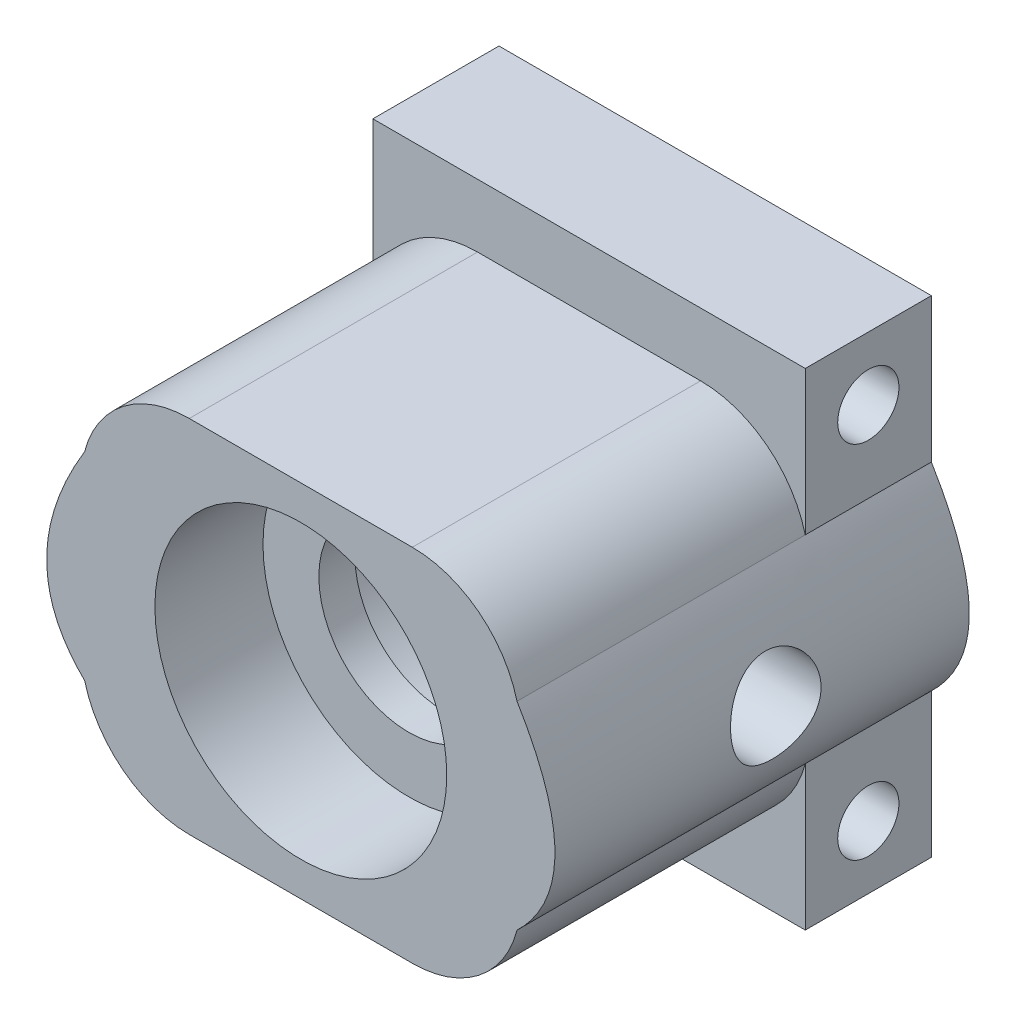
SolidWorks part; units mm, degrees
material "PLA"
ref_plane "Front Plane" through (0, 0, 0) normal (0, 0, 1) x (1, 0, 0)
ref_plane "Top Plane" through (0, 0, 0) normal (0, 1, 0) x (1, 0, 0)
ref_plane "Right Plane" through (0, 0, 0) normal (1, 0, 0) x (0, 0, -1)
sketch "Sketch1" plane through (0, 0, 0) normal (0, 0, 1) x (1, 0, 0)
  line L0 (-12, 13.5) -> (-12, 10)
  line L1 (-12, 10) -> (12, 10)
  line L2 (12, 10) -> (12, 13.5)
  line L3 (12, 13.5) -> (-12, 13.5)
  line L4 (-12, -10) -> (-12, -13.5)
  line L5 (-12, -13.5) -> (12, -13.5)
  line L6 (12, -13.5) -> (12, -10)
  line L7 (12, -10) -> (-12, -10)
  line L8 (0, 10.0333) -> (0, -15.702) construction
  line L9 (-12, 10) -> (-12, -10) construction
  line L10 (12, 10) -> (12, -10) construction
  line L11 (12, 10) -> (12, 5.5)
  line L12 (12, -10) -> (12, -5.5)
  line L13 (10, 10) -> (10, 5.5)
  line L14 (10, -10) -> (10, -5.5)
  line L17 (-10, -10) -> (-10, -5.5)
  line L18 (0, 0) -> (14.9553, 0) construction
  line L19 (-12, -10) -> (-12, -5.5)
  line L20 (-12, 10) -> (-12, 5.5)
  line L21 (-10, 10) -> (-10, 5.5)
  circle A0 centre (0, 0) radius 8.1
  circle A1 centre (0, 0) radius 5
  spline S0 degree 2 poles (12, 5.5) (16.2082, -1.4527) (12, -5.5) knots 0 0 0 0.703674 0.703674 0.703674
  spline S1 degree 2 poles (5.9341, -10) (5.4786, -10.0093) (0, -10) knots 0.968743 0.968743 0.968743 1 1 1
  spline S2 degree 2 poles (10, 5.5) (13.145, -1.5935) (10, -5.5) knots 0 0 0 0.703674 0.703674 0.703674
  spline S3 degree 2 poles (-12, 5.5) (-16.2082, -1.4527) (-12, -5.5) knots 0 0 0 0.703674 0.703674 0.703674
  spline S4 degree 2 poles (-10, 5.5) (-13.145, -1.5935) (-10, -5.5) knots 0 0 0 0.703674 0.703674 0.703674
  point P9 (0, -10)
  point P21 (12, 7.75)
  point P26 (0, 0)
  dimension "D6" = 8
  dimension "D8" = 16.2
  dimension "D9" = 10
  dimension "D5" = 8
  dimension "D1" = 3.5
  dimension "D2" = 3.5
  dimension "D3" = 24
  dimension "D4" = 27
  dimension "D7" = 2
extrude "Boss-Extrude1" add sketch "Sketch1" along normal blind 7 contours L2 L3 L0 L1 | S4 L21 L1 L20 S3 L19 L7 L17 | L13 S2 L14 L7 L12 S0 L11 L1 | L7 S1 L4 L5 L6 | L21 S4 L17 L7 L14 S2 L13 L1 A0 region at (0, 11.75, 0) region at (-11.7448, -0.0184, 0) region at (0, 9.6941, 0) region at (11.7448, -0.0184, 0) region at (-0.0008, -11.7504, 0)
extrude "Boss-Extrude2" add sketch "Sketch1<3>" along normal blind 16 from surface contours L21 S4 L17 L7 L14 S2 L13 L1 A0 | S4 L21 L1 L20 S3 L19 L7 L17 | L13 S2 L14 L7 L12 S0 L11 L1 region at (-11.7448, -0.0184, 0) region at (0, 9.6941, 0) region at (11.7448, -0.0184, 0) starting at face at (4.4506, -10, 7)
sketch "Sketch1<3>" plane through (0, 0, 0) normal (0, 0, 1) x (1, 0, 0) same geometry as "Sketch1"
sketch "Sketch2" plane through (-12, 0, 0) normal (-1, 0, 0) x (0, 0, 1)
  line L0 (7, -13.5) -> (0, -13.5) construction
  line L3 (3.5, 10) -> (3.5, -10) construction
  line L4 (7, -10) -> (7, -13.5) construction
  line L5 (0, -13.5) -> (0, -5.5) construction
  point P0 (3.5, 10)
  point P1 (3.5, -10)
  dimension "D1" = 20
  dimension "D2" = 3.5
hole_wizard "M3 Clearance Hole1" positions "Sketch3" profile "Sketch4" hole size "M3" standard "ISO" end condition through all
sketch "Sketch3" plane through (-12, 0, 0) normal (-1, 0, 0) x (0, 0, 1)
  point P0 (3.5, 10)
  point P3 (3.5, -10)
sketch "Sketch4" plane through (-12, 10, 3.5) normal (0, 1, 0) x (0, 0, 1)
  line L0 (0, 0) -> (0, 26.1041)
  line L1 (0, 26.1041) -> (1.7, 26.1041)
  line L2 (1.7, 26.1041) -> (1.7, 0)
  line L5 (1.7, 0) -> (0, 0)
  line L11 (0, -6.35) -> (0, 107.95) construction
  dimension "Thru Hole Dia." = 3.4
  dimension "Thru Hole Depth" = 26.1041
sketch "Sketch5" plane through (0, 13.5, 0) normal (0, 1, 0) x (1, 0, 0)
  line L0 (12, 0) -> (-12, 0) construction
  point P0 (0, -14)
  dimension "D1" = 14
fillet "Fillet1" radius 6 4 edges at (-12, 10, 15) (12, 10, 15) (12, -10, 15) (-12, -10, 15)
extrude "Boss-Extrude3" add sketch "Sketch1<4>" along normal blind 2 from offset 15 contours A0 A1 region at (-7.8709, 0, 0)
sketch "Sketch1<4>" plane through (0, 0, 0) normal (0, 0, 1) x (1, 0, 0) same geometry as "Sketch1"
fillet "Fillet2" radius 2 1 edges at (8.1, 0, 0)
sketch "Sketch6" plane through (0, 0, 0) normal (1, 0, 0) x (0, 0, -1)
  line L0 (0, -5.5) -> (0, 5.5) construction
  circle A0 centre (-10.7, 0) radius 2.5
  point P4 (0, 0)
  dimension "D1" = 5
  dimension "D2" = 10.7
extrude "Cut-Extrude1" cut sketch "Sketch6" against normal through all both and the other way through all
